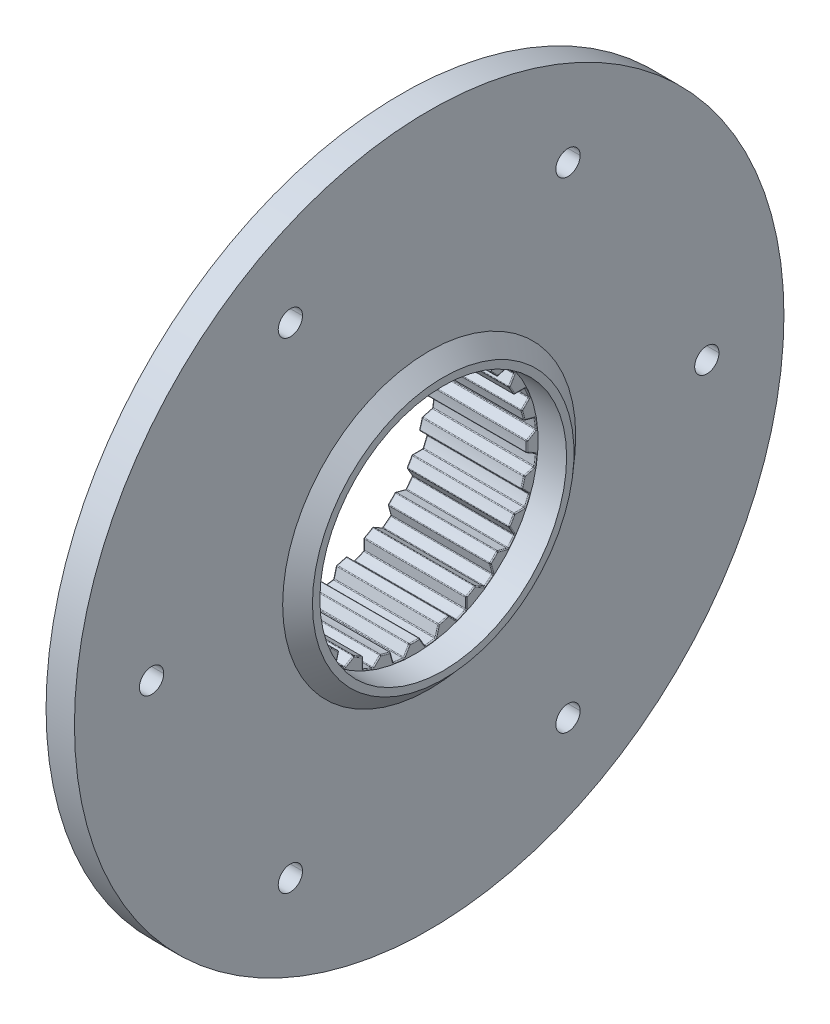
SolidWorks part; units mm, degrees
note: '?' marks a value the reader was unsure of.
other "Markup3"
sketch "Sketch36" plane through (0, -69.1592, 73.025) normal (-0.999, -0.0293, 0.0341) x (0.0318, -0.9965, 0.0767)
material "7075-T6 (SN)"
ref_plane "X-Y Datum" through (0, 0, 0) normal (0, 0, 1) x (1, 0, 0)
ref_plane "X-Z Datum" through (0, 0, 0) normal (0, 1, 0) x (1, 0, 0)
ref_plane "Y-Z Datum" through (0, 0, 0) normal (1, 0, 0) x (0, 0, -1)
sketch "Sketch1" plane through (0, 0, 0) normal (1, 0, 0) x (0, 0, -1)
  circle A0 centre (0, 0) radius 30.1625
extrude "Boss-Extrude1" add sketch "Sketch1" along normal blind 24.1096
sketch "Sketch2" plane through (24.1096, 0, 0) normal (1, 0, 0) x (0, 0, -1)
  circle A1 centre (0, 0) radius 73.025
  dimension "D4" = 146.05
extrude "Boss-Extrude2" add sketch "Sketch2" against normal blind 5.842 contours A1
sketch "Sketch3" plane through (0, 0, 0) normal (-1, 0, 0) x (0, 0, 1)
  circle A0 centre (0, 0) radius 25.1
  dimension "D1" = 50.2
extrude "Cut-Extrude1" cut sketch "Sketch3" against normal through all
sketch "Sketch4" plane through (0, 0, 0) normal (-1, 0, 0) x (0, 0, 1)
  line L0 (0, 0) -> (25.0052, 2.1797) construction
  line L1 (0, 0) -> (25.0052, -2.1797) construction
  line L2 (68.9218, 0) -> (-68.9218, 0) construction
  line L3 (25.0052, 2.1797) -> (23.0754, 1.0655)
  line L4 (25.0052, -2.1797) -> (23.0754, -1.0655)
  circle A0 centre (0, 0) radius 23.1 construction
  circle A1 centre (0, 0) radius 25.1 construction
  arc A2 (25.0052, 2.1797) -> (25.0052, -2.1797) centre (0, 0) cw
  arc A3 (23.0754, 1.0655) -> (23.0754, -1.0655) centre (0, 0) cw
  dimension "D1" = 9.964
  dimension "D3" = 46.2
  dimension "D2" = 4.982
  dimension "D4" = 60
extrude "Boss-Extrude3" add sketch "Sketch4" against normal up to surface (24.1096 mm away) up to face at (24.1096, 0, 25.1)
pattern_circular "CirPattern2" count 24 over 360 about axis through (0, 0, 0) along (1, 0, 0) of "Boss-Extrude3"
fillet "Fillet3" radius 3.81 1 edges at (0, 0, -30.1625)
sketch "Sketch8" plane through (24.1096, 0, 0) normal (1, 0, 0) x (0, 0, -1)
  line L0 (0, 0) -> (-57.15, 0) construction
  line L1 (68.9218, 0) -> (-68.9218, 0) construction
  dimension "D1" = 57.15
hole_wizard "Ø5.0 (5) Diameter Hole1" positions "Sketch9" profile "Sketch10" hole size "Ø5.0" standard "ANSI Metric" end condition through all
sketch "Sketch9" plane through (24.1096, 0, 0) normal (1, 0, 0) x (0, 0, -1)
  point P0 (-57.15, 0)
sketch "Sketch10" plane through (24.1096, 0, 57.15) normal (0, 1, 0) x (0, 0, -1)
  line L0 (0, 0) -> (0, 24.1096)
  line L1 (0, 24.1096) -> (2.5, 24.1096)
  line L2 (2.5, 24.1096) -> (2.5, 0)
  line L5 (2.5, 0) -> (0, 0)
  line L11 (0, -6.35) -> (0, 107.95) construction
  dimension "Thru Hole Dia." = 5
  dimension "Thru Hole Depth" = 24.1096
pattern_circular "CirPattern3" count 6 over 360 about axis through (0, 0, 0) along (1, 0, 0) of "Ø5.0 (5) Diameter Hole1"
sketch "Sketch11" plane through (24.1096, 0, 0) normal (1, 0, 0) x (0, 0, -1)
  circle A0 centre (0, 0) radius 25.4
  circle A1 centre (0, 0) radius 27.94
  circle A2 centre (0, 0) radius 30.1625
  dimension "D1" = 50.8
  dimension "D2" = 55.88
  dimension "D3" = 60.325
extrude "Boss-Extrude4" add sketch "Sketch11" along normal blind 2.8904 contours A1 A0 | A2 A1
sketch "Sketch13" plane through (0, 0, 0) normal (0, 0, 1) x (1, 0, 0)
  line L0 (24.1096, -27.7821) -> (25.7233, -27.7821) construction
  line L1 (24.1096, -27.94) -> (24.1096, 27.94) construction
  line L2 (24.1096, -30.1625) -> (24.1096, 30.1625) construction
  line L3 (24.1096, -30.1625) -> (25.9346, -30.1625) construction
  line L12 (27, -26.9226) -> (27, -30.1625)
  line L13 (27, -30.1625) -> (24.1096, -30.1625)
  line L15 (0, 0) -> (50000, 0) construction
  line L20 (24.1096, -30.1625) -> (27, -26.9226)
  dimension "D1" = 41.737
  dimension "D2" = 2.8758
revolve "Cut-Revolve2" cut sketch "Sketch13" angle 360 about L15
sketch "Sketch24" plane through (0, 0, 0) normal (0, 1, 0) x (1, 0, 0)
  line L0 (0, 0) -> (24.1096, 0) construction
  line L1 (24.1096, 25.4) -> (21.1261, 25.4)
  line L3 (24.1096, 0) -> (24.1096, 25.4) construction
  line L4 (24.1096, 25.4) -> (21.1261, 25.4) construction
  line L9 (24.1096, 23.1) -> (24.1096, 25.4)
  line L11 (21.1261, 25.4) -> (21.1261, 23.1)
  line L12 (24.1096, 23.1) -> (0, 23.1) construction
  line L13 (21.1261, 23.1) -> (24.1096, 23.1)
revolve "Cut-Revolve3" cut sketch "Sketch24" angle 360 about L0
fillet "Fillet8" radius 0.2 288 edges at (0, -23.1894, -9.6054) (0, -21.6308, -10.6149) (0, -20.0052, -11.55) (0, -20.0082, -13.4254) (0, -19.9132, -15.2799) (0, -18.1464, -15.8517) (0, -16.3342, -16.3342) (0, -15.8517, -18.1464) (0, -15.2799, -19.9132) (0, -13.4254, -20.0082) (0, -11.55, -20.0052) (0, -10.6149, -21.6308) (0, 3.2762, 24.8853) (0, -9.6054, -23.1894) (0, -7.7894, -22.8012) (0, -5.9787, -22.3129) (0, -4.6548, -23.6411) (0, -3.2762, -24.8853) (0, -1.6226, -24.0403) (0, 0, -23.1) (0, 1.6226, -24.0403) (0, 3.2762, -24.8853) (0, 4.6548, -23.6411) (0, 5.9787, -22.3129) (0, 7.7894, -22.8012) (0, 9.6054, -23.1894) (0, 10.6149, -21.6308) (0, 11.55, -20.0052) (0, 13.4254, -20.0082) (0, 15.2799, -19.9132) (0, 15.8517, -18.1464) (0, 16.3342, -16.3342) (0, 18.1464, -15.8517) (0, 1.6226, 24.0403) (0, 19.9132, -15.2799) (0, 0, 23.1) (0, 20.0082, -13.4254) (0, 20.0052, -11.55) (0, 21.6308, -10.6149) (0, -1.6226, 24.0403) (0, 23.1894, -9.6054) (0, 22.8012, -7.7894) (0, 22.3129, -5.9787) (0, 23.6411, -4.6548) (0, 24.8853, -3.2762) (0, 24.0403, -1.6226) (0, 23.1, 0) (0, 24.0403, 1.6226) (0, 24.8853, 3.2762) (0, 23.6411, 4.6548) (0, 22.3129, 5.9787) (0, 22.8012, 7.7894) (0, 23.1894, 9.6054) (0, 21.6308, 10.6149) (0, 20.0052, 11.55) (0, 20.0082, 13.4254) (0, 19.9132, 15.2799) (0, 18.1464, 15.8517) (0, 16.3342, 16.3342) (0, 15.8517, 18.1464) (0, 15.2799, 19.9132) (0, 13.4254, 20.0082) (0, 11.55, 20.0052) (0, 10.6149, 21.6308) (0, 9.6054, 23.1894) (0, 7.7894, 22.8012) (0, 5.9787, 22.3129) (0, 4.6548, 23.6411) (0, -3.2762, 24.8853) (0, -4.6548, 23.6411) (0, -5.9787, 22.3129) (0, -7.7894, 22.8012) (10.5631, 4.9431, 22.5649) (10.5631, 4.3664, 24.7173) (21.1261, 4.6548, 23.6411) (10.5631, 7.0016, 22.0134) (10.5631, 8.5772, 23.589) (10.5631, 10.6149, 20.5167) (10.5631, 10.6149, 22.745) (10.5631, 12.4605, 19.4511) (10.5631, 14.3903, 20.5653) (10.5631, 15.5633, 17.0702) (10.5631, 16.1401, 19.2226) (10.5631, 17.0702, 15.5633) (10.5631, 19.2226, 16.1401) (10.5631, 19.4511, 12.4605) (10.5631, 20.5653, 14.3903) (10.5631, 20.5167, 10.6149) (10.5631, 22.745, 10.6149) (10.5631, 22.0134, 7.0016) (10.5631, 23.589, 8.5772) (10.5631, 22.5649, 4.9431) (10.5631, 24.7173, 4.3664) (10.5631, 23.0754, 1.0655) (10.5631, 25.0052, 2.1797) (10.5631, 23.0754, -1.0655) (10.5631, 25.0052, -2.1797) (10.5631, 22.5649, -4.9431) (10.5631, 24.7173, -4.3664) (10.5631, 22.0134, -7.0016) (10.5631, 23.589, -8.5772) (10.5631, 20.5167, -10.6149) (10.5631, 22.745, -10.6149) (10.5631, 19.4511, -12.4605) (10.5631, 20.5653, -14.3903) (10.5631, 17.0702, -15.5633) (10.5631, 19.2226, -16.1401) (10.5631, 15.5633, -17.0702) (0, -9.6054, 23.1894) (10.5631, 16.1401, -19.2226) (10.5631, 12.4605, -19.4511) (10.5631, 14.3903, -20.5653) (10.5631, 10.6149, -20.5167) (10.5631, 10.6149, -22.745) (10.5631, 7.0016, -22.0134) (10.5631, 8.5772, -23.589) (10.5631, 4.9431, -22.5649) (10.5631, 4.3664, -24.7173) (10.5631, 1.0655, -23.0754) (10.5631, 2.1797, -25.0052) (10.5631, -1.0655, -23.0754) (10.5631, -2.1797, -25.0052) (10.5631, -4.9431, -22.5649) (10.5631, -4.3664, -24.7173) (10.5631, -7.0016, -22.0134) (10.5631, -8.5772, -23.589) (10.5631, -10.6149, -20.5167) (10.5631, -10.6149, -22.745) (10.5631, -12.4605, -19.4511) (10.5631, -14.3903, -20.5653) (10.5631, -15.5633, -17.0702) (10.5631, -16.1401, -19.2226) (10.5631, -17.0702, -15.5633) (10.5631, -19.2226, -16.1401) (10.5631, -19.4511, -12.4605) (10.5631, -20.5653, -14.3903) (10.5631, -20.5167, -10.6149) (10.5631, -22.745, -10.6149) (10.5631, -22.0134, -7.0016) (10.5631, -23.589, -8.5772) (10.5631, -22.5649, -4.9431) (10.5631, -24.7173, -4.3664) (10.5631, -23.0754, -1.0655) (10.5631, -25.0052, -2.1797) (0, -10.6149, 21.6308) (10.5631, -23.0754, 1.0655) (10.5631, -25.0052, 2.1797) (10.5631, -22.5649, 4.9431) (10.5631, -24.7173, 4.3664) (10.5631, -22.0134, 7.0016) (0, -11.55, 20.0052) (10.5631, -23.589, 8.5772) (10.5631, -20.5167, 10.6149) (10.5631, -22.745, 10.6149) (10.5631, -19.4511, 12.4605) (10.5631, -20.5653, 14.3903) (0, -13.4254, 20.0082) (10.5631, -17.0702, 15.5633) (10.5631, -19.2226, 16.1401) (10.5631, -15.5633, 17.0702) (10.5631, -16.1401, 19.2226) (10.5631, -12.4605, 19.4511) (10.5631, -14.3903, 20.5653) (10.5631, -10.6149, 20.5167) (10.5631, -10.6149, 22.745) (10.5631, -7.0016, 22.0134) (10.5631, -8.5772, 23.589) (10.5631, -4.9431, 22.5649) (10.5631, -4.3664, 24.7173) (10.5631, -1.0655, 23.0754) (10.5631, -2.1797, 25.0052) (10.5631, 1.0655, 23.0754) (10.5631, 2.1797, 25.0052) (21.1261, -3.2762, 24.8853) (21.1261, -9.6054, 23.1894) (21.1261, -15.2799, 19.9132) (21.1261, -19.9132, 15.2799) (21.1261, -23.1894, 9.6054) (21.1261, -24.8853, 3.2762) (21.1261, -24.8853, -3.2762) (21.1261, -23.1894, -9.6054) (21.1261, -19.9132, -15.2799) (21.1261, -15.2799, -19.9132) (21.1261, -9.6054, -23.1894) (21.1261, -3.2762, -24.8853) (21.1261, 3.2762, -24.8853) (21.1261, 9.6054, -23.1894) (21.1261, 15.2799, -19.9132) (21.1261, 19.9132, -15.2799) (21.1261, 23.1894, -9.6054) (21.1261, 24.8853, -3.2762) (21.1261, 24.8853, 3.2762) (21.1261, 23.1894, 9.6054) (21.1261, 19.9132, 15.2799) (21.1261, 15.2799, 19.9132) (21.1261, 9.6054, 23.1894) (21.1261, 3.2762, 24.8853) (21.1261, 0, 23.1) (21.1261, -5.9787, 22.3129) (21.1261, -11.55, 20.0052) (21.1261, -16.3342, 16.3342) (21.1261, -20.0052, 11.55) (21.1261, -22.3129, 5.9787) (21.1261, -23.1, 0) (21.1261, -22.3129, -5.9787) (21.1261, -20.0052, -11.55) (21.1261, -16.3342, -16.3342) (21.1261, -11.55, -20.0052) (21.1261, -5.9787, -22.3129) (21.1261, 0, -23.1) (21.1261, 5.9787, -22.3129) (21.1261, 11.55, -20.0052) (21.1261, 16.3342, -16.3342) (21.1261, 20.0052, -11.55) (21.1261, 22.3129, -5.9787) (21.1261, 23.1, 0) (21.1261, 22.3129, 5.9787) (21.1261, 20.0052, 11.55) (21.1261, 16.3342, 16.3342) (21.1261, 11.55, 20.0052) (21.1261, -1.6226, 24.0403) (21.1261, -4.6548, 23.6411) (21.1261, -7.7894, 22.8012) (21.1261, -10.6149, 21.6308) (21.1261, -13.4254, 20.0082) (21.1261, -15.8517, 18.1464) (21.1261, -18.1464, 15.8517) (21.1261, -20.0082, 13.4254) (21.1261, -21.6308, 10.6149) (21.1261, -22.8012, 7.7894) (21.1261, -23.6411, 4.6548) (21.1261, -24.0403, 1.6226) (21.1261, -24.0403, -1.6226) (21.1261, -23.6411, -4.6548) (21.1261, -22.8012, -7.7894) (21.1261, -21.6308, -10.6149) (21.1261, -20.0082, -13.4254) (21.1261, -18.1464, -15.8517) (21.1261, -15.8517, -18.1464) (21.1261, -13.4254, -20.0082) (21.1261, -10.6149, -21.6308) (21.1261, -7.7894, -22.8012) (21.1261, -4.6548, -23.6411) (21.1261, -1.6226, -24.0403) (21.1261, 1.6226, -24.0403) (21.1261, 4.6548, -23.6411) (21.1261, 7.7894, -22.8012) (21.1261, 10.6149, -21.6308) (21.1261, 13.4254, -20.0082) (21.1261, 15.8517, -18.1464) (21.1261, 18.1464, -15.8517) (21.1261, 20.0082, -13.4254) (21.1261, 21.6308, -10.6149) (21.1261, 22.8012, -7.7894) (21.1261, 23.6411, -4.6548) (21.1261, 24.0403, -1.6226) (21.1261, 24.0403, 1.6226) (21.1261, 23.6411, 4.6548) (21.1261, 22.8012, 7.7894) (21.1261, 21.6308, 10.6149) (21.1261, 20.0082, 13.4254) (21.1261, 18.1464, 15.8517) (21.1261, 15.8517, 18.1464) (21.1261, 13.4254, 20.0082) (21.1261, 10.6149, 21.6308) (21.1261, 7.7894, 22.8012) (21.1261, 1.6226, 24.0403) (21.1261, 5.9787, 22.3129) (0, -15.2799, 19.9132) (0, -15.8517, 18.1464) (0, -16.3342, 16.3342) (0, -18.1464, 15.8517) (0, -19.9132, 15.2799) (0, -20.0082, 13.4254) (0, -20.0052, 11.55) (0, -21.6308, 10.6149) (0, -23.1894, 9.6054) (0, -22.8012, 7.7894) (0, -22.3129, 5.9787) (0, -23.6411, 4.6548) (0, -24.8853, 3.2762) (0, -24.0403, 1.6226) (0, -23.1, 0) (0, -24.0403, -1.6226) (0, -24.8853, -3.2762) (0, -23.6411, -4.6548) (0, -22.3129, -5.9787) (0, -22.8012, -7.7894)
ref_axis "Axis1" through (-54.8034, 0, 0) along (1, 0, 0)?
ref_point "Point1"
ref_point "Point5"
ref_plane "Plane2" through (0, -49.4934, 0) normal (0, 1, 0) x (1, 0, 0)
ref_point "Point2"
ref_point "Point3"
ref_point "Point4"
ref_point "Point6"
split line "Split Line2"
ref_plane "Plane3" through (0, 49.4934, 0) normal (0, 1, 0) x (1, 0, 0)
split line "Split Line1"
split line "Split Line3"
ref_plane "Plane4" through (0, 0, 0) normal (0, -0.866, 0.5) x (1, 0, 0)
ref_plane "Plane5" through (0, 0, 0) normal (0, -0.866, -0.5) x (1, 0, 0)
ref_plane "Plane8" through (0, 0, 0) normal (0, -0.5, -0.866) x (1, 0, 0)
ref_plane "Plane7" through (0, 0, 0) normal (0, -0.5, 0.866) x (1, 0, 0)
split line "Split Line5" [suppressed]
split line "Split Line4" [suppressed]
other "Graphic1" [suppressed]
other "Graphic (Closed) -1"
other "Graphic (Closed) -2"
other "Graphic (Closed) -3"
other "Graphic (Closed) -4"
other "Graphic2" [suppressed]
other "Graphic (Closed) -5" [suppressed]
other "Graphic (Closed) -6" [suppressed]
other "Graphic (Closed) -7" [suppressed]
other "Graphic (Closed) -8" [suppressed]
other "Graphic (Closed) -9" [suppressed]
other "Graphic (Closed) -10" [suppressed]
other "Graphic (Closed) -11" [suppressed]
other "Graphic (Closed) -12" [suppressed]
other "Graphic (Closed) -13" [suppressed]
other "Graphic (Closed) -14" [suppressed]
other "Graphic (Closed) -15" [suppressed]
other "Graphic (Closed) -16" [suppressed]
other "Graphic (Closed) -17" [suppressed]
other "Graphic (Closed) -18" [suppressed]
other "Graphic (Closed) -19" [suppressed]
other "Graphic (Closed) -20" [suppressed]
other "Graphic (Closed) -21" [suppressed]
other "Graphic (Closed) -22" [suppressed]
other "Graphic (Closed) -23" [suppressed]
other "Graphic (Closed) -24" [suppressed]
other "Graphic (Closed) -25" [suppressed]
other "Graphic (Closed) -26" [suppressed]
sketch "Sketch37" [suppressed] plane through (18.2676, 0, 0) normal (-1, 0, 0) x (0, 0, 1)
  line L0 (0, 0) -> (57.15, 0) construction
  line L1 (11.8542, 23.5358) -> (59.0097, 4.6413)
  line L2 (33.7787, -9.9624) -> (52.7438, -2.3634)
  line L3 (68.9218, 0) -> (-68.9218, 0) construction
  line L4 (11.8542, -23.5358) -> (59.0097, -4.6413)
  line L5 (35.432, 14.0885) -> (33.7787, 9.9624) construction
  line L6 (35.432, -14.0885) -> (33.7787, -9.9624) construction
  line L7 (33.7787, 9.9624) -> (52.7438, 2.3634)
  line L8 (33.7787, 9.9624) -> (21.8407, 14.7458)
  line L9 (33.7787, -9.9624) -> (21.8407, -14.7458)
  line L10 (25.5171, -24.272) -> (28.4187, -44.4958)
  line L11 (8.2616, -34.2344) -> (24.3252, -46.8592)
  line L12 (8.2616, -34.2344) -> (-1.8499, -26.2875)
  line L13 (25.5171, -24.272) -> (23.6906, -11.5417)
  line L14 (26.3097, 1.5018) -> (33.5243, -48.7832)
  line L15 (-14.4555, -22.0339) -> (25.4854, -53.4245)
  line L16 (-8.2616, -34.2344) -> (-24.3252, -46.8592)
  line L17 (-25.5171, -24.272) -> (-28.4187, -44.4958)
  line L18 (-25.5171, -24.272) -> (-23.6906, -11.5417)
  line L19 (-8.2616, -34.2344) -> (1.8499, -26.2875)
  line L20 (14.4555, -22.0339) -> (-25.4854, -53.4245)
  line L21 (-26.3097, 1.5018) -> (-33.5243, -48.7832)
  line L22 (-33.7787, -9.9624) -> (-52.7438, -2.3634)
  line L23 (-33.7787, 9.9624) -> (-52.7438, 2.3634)
  line L24 (-33.7787, 9.9624) -> (-21.8407, 14.7458)
  line L25 (-33.7787, -9.9624) -> (-21.8407, -14.7458)
  line L26 (-11.8542, -23.5358) -> (-59.0097, -4.6413)
  line L27 (-11.8542, 23.5358) -> (-59.0097, 4.6413)
  line L28 (-25.5171, 24.272) -> (-28.4187, 44.4958)
  line L29 (-8.2616, 34.2344) -> (-24.3252, 46.8592)
  line L30 (-8.2616, 34.2344) -> (1.8499, 26.2875)
  line L31 (-25.5171, 24.272) -> (-23.6906, 11.5417)
  line L32 (-26.3097, -1.5018) -> (-33.5243, 48.7832)
  line L33 (14.4555, 22.0339) -> (-25.4854, 53.4245)
  line L34 (8.2616, 34.2344) -> (24.3252, 46.8592)
  line L35 (25.5171, 24.272) -> (28.4187, 44.4958)
  line L36 (25.5171, 24.272) -> (23.6906, 11.5417)
  line L37 (8.2616, 34.2344) -> (-1.8499, 26.2875)
  line L38 (-14.4555, 22.0339) -> (25.4854, 53.4245)
  line L39 (26.3097, -1.5018) -> (33.5243, 48.7832)
  circle A0 centre (57.15, 0) radius 5
  circle A1 centre (0, 0) radius 26.3525 construction
  circle A3 centre (28.575, -49.4934) radius 5
  arc A4 (11.8542, 23.5358) -> (11.8542, -23.5358) centre (0, 0) cw
  arc A5 (26.3097, 1.5018) -> (-14.4555, -22.0339) centre (0, 0) cw
  circle A6 centre (-28.575, -49.4934) radius 5
  arc A7 (14.4555, -22.0339) -> (-26.3097, 1.5018) centre (0, 0) cw
  circle A8 centre (-57.15, 0) radius 5
  arc A9 (-11.8542, -23.5358) -> (-11.8542, 23.5358) centre (0, 0) cw
  circle A10 centre (-28.575, 49.4934) radius 5
  arc A11 (-26.3097, -1.5018) -> (14.4555, 22.0339) centre (0, 0) cw
  circle A12 centre (28.575, 49.4934) radius 5
  arc A13 (-14.4555, 22.0339) -> (26.3097, -1.5018) centre (0, 0) cw
  point P84 (0, 0)
  point P106 (0, 0)
  circle M17 centre (0, 0) radius 73.025
  circle M85 centre (0, 0) radius 30.1625
  dimension "D1" = 50.8
  dimension "D2" = 10
  dimension "D3" = 6
  dimension "D4" = 4.445
  dimension "D5" = 4.445
extrude "Cut-Extrude3" [suppressed] cut sketch "Sketch37" against normal blind 17.78 contours A12 L39 L1 A0 L4 L14 A3 L15 L20 A6 L21 L26 A8 L27 L32 A10 L33 L38 M17 M85
fillet "Fillet9" [suppressed] radius 12.7
fillet "Fillet10" [suppressed] radius 3.2004
sketch "Sketch38" [suppressed] plane through (18.2676, 0, -18.0136) normal (-1, 0, 0) x (0, 0, 1)
  line L0 (11.6636, 0) -> (75.1636, 0) construction
  line L1 (31.2986, 17.5762) -> (76.5218, 4.812)
  line L2 (52.7718, -7.1607) -> (70.6348, -2.1189)
  line L4 (31.2986, -17.5762) -> (76.5218, -4.812)
  line L5 (53.9102, 11.1941) -> (52.7718, 7.1607) construction
  line L6 (53.9102, -11.1941) -> (52.7718, -7.1607) construction
  line L7 (52.7718, 7.1607) -> (70.6348, 2.1189)
  line L8 (52.7718, 7.1607) -> (35.04, 12.1654)
  line L9 (52.7718, -7.1607) -> (35.04, -12.1654)
  line L10 (38.419, -32.0204) -> (42.9842, -50.0111)
  line L11 (26.0164, -39.181) -> (39.3142, -52.13)
  line L12 (26.0164, -39.181) -> (12.8163, -26.3273)
  line L13 (38.419, -32.0204) -> (33.8874, -14.1619)
  line L14 (36.7025, -8.2163) -> (48.26, -53.7628)
  line L15 (6.2597, -25.7925) -> (39.9254, -58.5748)
  line L16 (-2.6892, -39.181) -> (-15.987, -52.13)
  line L17 (-15.0918, -32.0204) -> (-19.657, -50.0111)
  line L18 (-15.0918, -32.0204) -> (-10.5602, -14.1619)
  line L19 (-2.6892, -39.181) -> (10.5109, -26.3273)
  line L20 (17.0675, -25.7925) -> (-16.5982, -58.5748)
  line L21 (-13.3753, -8.2163) -> (-24.9328, -53.7628)
  line L22 (-29.4446, -7.1607) -> (-47.3076, -2.1189)
  line L23 (-29.4446, 7.1607) -> (-47.3076, 2.1189)
  line L24 (-29.4446, 7.1607) -> (-11.7128, 12.1654)
  line L25 (-29.4446, -7.1607) -> (-11.7128, -12.1654)
  line L26 (-7.9714, -17.5762) -> (-53.1946, -4.812)
  line L27 (-7.9714, 17.5762) -> (-53.1946, 4.812)
  line L28 (-15.0918, 32.0204) -> (-19.657, 50.0111)
  line L29 (-2.6892, 39.181) -> (-15.987, 52.13)
  line L30 (-2.6892, 39.181) -> (10.5109, 26.3273)
  line L31 (-15.0918, 32.0204) -> (-10.5602, 14.1619)
  line L32 (-13.3753, 8.2163) -> (-24.9328, 53.7628)
  line L33 (17.0675, 25.7925) -> (-16.5982, 58.5748)
  line L34 (26.0164, 39.181) -> (39.3142, 52.13)
  line L35 (38.419, 32.0204) -> (42.9842, 50.0111)
  line L36 (38.419, 32.0204) -> (33.8874, 14.1619)
  line L37 (26.0164, 39.181) -> (12.8163, 26.3273)
  line L38 (6.2597, 25.7925) -> (39.9254, 58.5748)
  line L39 (36.7025, 8.2163) -> (48.26, 53.7628)
  circle A0 centre (75.1636, 0) radius 5
  circle A3 centre (43.4136, -54.9926) radius 5
  arc A4 (31.2986, 17.5762) -> (31.2986, -17.5762) centre (11.6636, 0) cw
  arc A5 (36.7025, -8.2163) -> (6.2597, -25.7925) centre (11.6636, 0) cw
  circle A6 centre (-20.0864, -54.9926) radius 5
  arc A7 (17.0675, -25.7925) -> (-13.3753, -8.2163) centre (11.6636, 0) cw
  circle A8 centre (-51.8364, 0) radius 5
  arc A9 (-7.9714, -17.5762) -> (-7.9714, 17.5762) centre (11.6636, 0) cw
  circle A10 centre (-20.0864, 54.9926) radius 5
  arc A11 (-13.3753, 8.2163) -> (17.0675, 25.7925) centre (11.6636, 0) cw
  circle A12 centre (43.4136, 54.9926) radius 5
  arc A13 (6.2597, 25.7925) -> (36.7025, 8.2163) centre (11.6636, 0) cw
  arc A14 (72.6636, 0) -> (77.6636, 0) centre (75.1636, 0) ccw construction
  point P84 (11.6636, 0)
  point P106 (0, 0)
  circle M127 centre (18.0136, 0) radius 33.3629
  dimension "D1" = 46.99
  dimension "D2" = 10
  dimension "D3" = 6
  dimension "D4" = 4.191
  dimension "D5" = 4.191
extrude "Cut-Extrude4" [suppressed] cut sketch "Sketch38" against normal blind 17.78 contours A0 L7 L8 L9 L2 M127 | A3 L10 L13 L12 L11 M127 | A6 L16 L19 L18 L17 M127 | A8 L22 L25 L24 L23 M127 | A10 L28 L31 L30 L29 M127 | A12 L34 L37 L36 L35 M127
fillet "Fillet11" [suppressed] radius 3.2004
fillet "Fillet12" [suppressed] radius 3.175
sketch "Sketch39" [suppressed] plane through (18.2676, 0, 0) normal (-1, 0, 0) x (0, 0, 1)
  line L0 (18.4652, 29.3547) -> (30.7368, 21.1527) construction
  line L4 (34.3607, 5.8298) -> (18.4652, 29.3547) construction
  line L7 (34.3607, 5.8298) -> (33.6872, 16.0425) construction
  arc A4 (15.6669, 29.4556) -> (20.2718, 31.494) centre (17.1697, 32.2812) ccw construction
  arc A6 (37.277, 6.4497) -> (33.2209, 3.0747) centre (36.4077, 3.3696) ccw construction
  arc A7 (30.3384, 26.5775) -> (38.186, 12.985) centre (42.9096, 24.7739) ccw construction
  circle A8 centre (24.601, 25.2537) radius 1.5875
  circle A9 centre (34.0239, 10.9361) radius 1.5875
extrude "Cut-Extrude5" [suppressed] cut sketch "Sketch39" against normal through all
pattern_circular "CirPattern4" [suppressed] count 6 over 360
